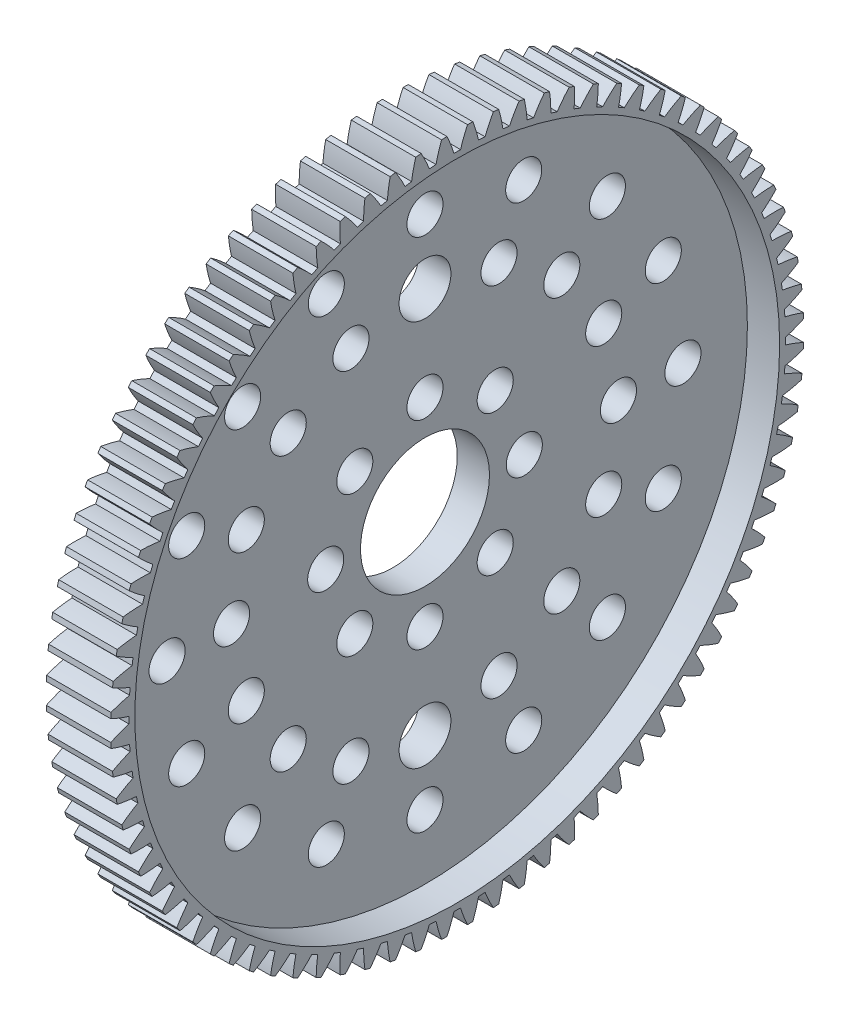
SolidWorks part; units mm, degrees
ref_plane "Plane1" through (0, 0, 0) normal (0, 0, 1) x (1, 0, 0)
ref_plane "Plane2" through (0, 0, 0) normal (0, 1, 0) x (1, 0, 0)
ref_plane "Plane3" through (0, 0, 0) normal (1, 0, 0) x (0, 0, -1)
sketch "HoldingSke" plane through (0, 0, 0) normal (0, 1, 0) x (1, 0, 0)
  line L0 (0, 0) -> (84.9607, -808.3474)
  line L1 (-15, 0) -> (100, 0) construction
  line L2 (0, 0) -> (-2.1039, 2.3779)
  line L3 (0, 0) -> (-11.863, 4.5341)
  line L4 (0, 0) -> (0.9027, 8.5887)
  line L5 (0, 0) -> (-47.5972, -17.7524)
  line L6 (0, 0) -> (-5.2639, -3.5516)
  line L7 (-2.1039, 2.3779) -> (8.8308, 51.9871)
  line L8 (-76.2, 54.61) -> (-61.976, 54.61)
  line L9 (-71.009, 38.7566) -> (-53.1078, 45.2721)
  line L10 (-76.2, 71.12) -> (104.1128, 71.12)
  line L11 (0, 0) -> (-6.35, 0)
  line L12 (-76.2, 101.6) -> (-76.1716, 101.6)
  line L13 (24.9733, 27.94) -> (52.9518, 28.4284)
  line L14 (24.9733, 27.94) -> (25.0241, 27.9398)
  line L15 (24.9733, 27.94) -> (100.4021, 29.52)
  circle A0 centre (0, 0) radius 6.35
  circle A1 centre (0, 0) radius 32.3342
  circle A2 centre (0, 0) radius 38.1
  circle A3 centre (0, 0) radius 6.35
  dimension "MHD" = 64.6684
  dimension "Hub_dia" = 76.2
  dimension "Bore" = 12.7
  dimension "MBD" = 12.7
  dimension "Num_teeth" = 84
  dimension "Pitch_radius" = 180.3128
  dimension "Pitch" = 812.8
  dimension "Width" = 6.35
  dimension "Overall_len" = 50.8
  dimension "Show_teeth" = 84
  dimension "Thickness" = 6.35
  dimension "OAL" = 50.8001
  dimension "T_dim" = 14.224
  dimension "Ap" = 20
  dimension "H" = 19.05
  dimension "Backlash" = 0.0284
  dimension "Addendum_fac" = 1
  dimension "Dedendum_fac" = 1.2
  dimension "Clearance_fac" = 0.2
  dimension "Dedendum_add" = 0.0508
sketch "BasProSke" plane through (0, 0, 0) normal (0, 1, 0) x (1, 0, 0)
  line L0 (-10, 0) -> (60, 0) construction
  line L1 (0, 0) -> (0, 34.1313)
  line L2 (0, 0) -> (6.35, 0)
  line L3 (6.35, 0) -> (6.35, 34.1313)
  line L4 (6.35, 34.1313) -> (0, 34.1313)
  dimension "Diameter" = 68.2625
  dimension "Thickness" = 6.35
revolve "Base-Revolve" add sketch "BasProSke" angle 360 about L0
sketch "TooCutSke" plane through (0, 0, 0) normal (1, 0, 0) x (0, 0, -1)
  line L1 (0, 0) -> (0, 107) construction
  line L2 (0, 0) -> (-0.6732, 33.3307) construction
  line L3 (0, 0) -> (-2.4927, 66.6185) construction
  line L4 (-0.6732, 33.3307) -> (-1.2463, 33.3093) construction
  arc A0 (0.3267, 32.3325) -> (-0.3267, 32.3325) centre (0, 0) ccw
  arc A1 (1.0224, 34.1413) -> (-1.0224, 34.1413) centre (0, 0) ccw
  circle A2 centre (0, 0) radius 33.3375 construction
  circle A3 centre (0, 0) radius 31.327 construction
  arc A4 (-0.3267, 32.3325) -> (-1.0224, 34.1413) centre (-13.0876, 28.4622) ccw
  arc A5 (1.0224, 34.1413) -> (0.3267, 32.3325) centre (13.0876, 28.4622) ccw
  dimension "Root_dia" = 64.6684
  dimension "Overcut_dia" = 68.3133
  dimension "Pitch_dia" = 66.675
  dimension "Base_dia" = 62.654
  dimension "Flank_rad" = 13.335
  dimension "Half_ang" = 2.143
  dimension "Half_CT" = 0.5736
extrude "ToothCut" cut sketch "TooCutSke" along normal through all
fillet "Breaks" [suppressed] radius 0.0159 tangent propagation no
fillet "RootFillets" [suppressed] radius 0.2095
pattern_circular "TeethCuts" count 84 every 4.286 about axis through (-10, 0, 0) along (1, 0, 0) of "ToothCut", "RootFillets", "Breaks"
sketch "HubNeaOneSke" plane through (0, 0, 0) normal (-1, 0, 0) x (0, 0, 1)
  circle A0 centre (0, 0) radius 32.3342
  dimension "Diameter" = 64.6684
extrude "HubNearOne" [suppressed] add sketch "HubNeaOneSke" along normal blind 44.4501
sketch "HubNeaBotSke" plane through (0, 0, 0) normal (-1, 0, 0) x (0, 0, 1)
  circle A0 centre (0, 0) radius 32.3342
  dimension "Diameter" = 64.6684
extrude "HubNearBoth" [suppressed] add sketch "HubNeaBotSke" along normal blind 22.225
ref_plane "FarPln" through (6.35, 0, 0) normal (1, 0, 0) x (0, 0, -1)
sketch "HubFarSke" plane through (6.35, 0, 0) normal (1, 0, 0) x (0, 0, -1)
  circle A0 centre (0, 0) radius 32.3342
  dimension "Diameter" = 64.6684
extrude "HubFar" [suppressed] add sketch "HubFarSke" along normal blind 22.225
sketch "BorSke" plane through (0, 0, 0) normal (1, 0, 0) x (0, 0, -1)
  circle A0 centre (0, 0) radius 6.35
  dimension "Diameter" = 12.7
extrude "Bore" cut sketch "BorSke" along normal mid plane 101.6001
sketch "KeySke" plane through (0, 0, 0) normal (1, 0, 0) x (0, 0, -1)
  line L0 (-1.5875, 0) -> (-1.5875, 7.874)
  line L1 (-1.5875, 7.874) -> (1.5875, 7.874)
  line L2 (1.5875, 7.874) -> (1.5875, 0)
  line L3 (0, 0) -> (0, 34) construction
  line L4 (-1.5875, 0) -> (1.5875, 0)
  dimension "Offset" = 7.874
  dimension "Width" = 3.175
extrude "Keyway" [suppressed] cut sketch "KeySke" along normal mid plane 101.6001
pattern_circular "Keyway2" [suppressed] count 2 every 90 about axis through (-10, 0, 0) along (1, 0, 0)
sketch "Sketch1" plane through (6.35, 0, 0) normal (1, 0, 0) x (0, 0, -1)
  line L0 (0, 0) -> (0, 50.8) construction
  circle A0 centre (0, 9.779) radius 1.778
  circle A1 centre (0, 19.05) radius 1.778
  circle A2 centre (0, 25.4) radius 1.778
  circle A3 centre (6.9148, 6.9148) radius 1.778
  circle A4 centre (9.779, 0) radius 1.778
  circle A5 centre (6.9148, -6.9148) radius 1.778
  circle A6 centre (0, -9.779) radius 1.778
  circle A7 centre (-6.9148, -6.9148) radius 1.778
  circle A8 centre (-9.779, 0) radius 1.778
  circle A9 centre (-6.9148, 6.9148) radius 1.778
  circle A10 centre (7.2901, 17.5999) radius 1.778
  circle A11 centre (9.7202, 23.4665) radius 1.778
  circle A12 centre (13.4704, 13.4704) radius 1.778
  circle A13 centre (17.9605, 17.9605) radius 1.778
  circle A14 centre (17.5999, 7.2901) radius 1.778
  circle A15 centre (23.4665, 9.7202) radius 1.778
  circle A16 centre (19.05, 0) radius 1.778
  circle A17 centre (25.4, 0) radius 1.778
  circle A18 centre (17.5999, -7.2901) radius 1.778
  circle A19 centre (23.4665, -9.7202) radius 1.778
  circle A20 centre (13.4704, -13.4704) radius 1.778
  circle A21 centre (17.9605, -17.9605) radius 1.778
  circle A22 centre (7.2901, -17.5999) radius 1.778
  circle A23 centre (9.7202, -23.4665) radius 1.778
  circle A24 centre (0, -19.05) radius 1.778
  circle A25 centre (0, -25.4) radius 1.778
  circle A26 centre (-7.2901, -17.5999) radius 1.778
  circle A27 centre (-9.7202, -23.4665) radius 1.778
  circle A28 centre (-13.4704, -13.4704) radius 1.778
  circle A29 centre (-17.9605, -17.9605) radius 1.778
  circle A30 centre (-17.5999, -7.2901) radius 1.778
  circle A31 centre (-23.4665, -9.7202) radius 1.778
  circle A32 centre (-19.05, 0) radius 1.778
  circle A33 centre (-25.4, 0) radius 1.778
  circle A34 centre (-17.5999, 7.2901) radius 1.778
  circle A35 centre (-23.4665, 9.7202) radius 1.778
  circle A36 centre (-13.4704, 13.4704) radius 1.778
  circle A37 centre (-17.9605, 17.9605) radius 1.778
  circle A38 centre (-7.2901, 17.5999) radius 1.778
  circle A39 centre (-9.7202, 23.4665) radius 1.778
  point P25 (0, 0)
  point P86 (0, 0)
  dimension "D1" = 50.8
  dimension "D2" = 9.779
  dimension "D3" = 19.05
  dimension "D4" = 25.4
  dimension "D5" = 3.556
  dimension "D6" = 3.556
  dimension "D7" = 3.556
  dimension "D8" = 8
  dimension "D9" = 16
extrude "Cut-Extrude1" cut sketch "Sketch1" against normal through all
sketch "Sketch2" plane through (6.35, 0, 0) normal (1, 0, 0) x (0, 0, -1)
  circle A0 centre (0, 0) radius 31.75
  dimension "D1" = 63.5
extrude "Cut-Extrude2" cut sketch "Sketch2" against normal blind 3.175
hole_wizard "1/4-20 Tapped Hole1" positions "3DSketch1" profile "Sketch3" tap size "1/4-20" standard "ANSI Inch"
sketch3d "3DSketch1"
  line L0 (0, 19.05, 0) -> (3.175, 19.05, 0) construction
  line L1 (0, -19.05, 0) -> (3.175, -19.05, 0) construction
  point P0 (3.175, 19.05, 0)
  point P4 (3.175, -19.05, 0)
sketch "Sketch3" plane through (3.175, 19.05, 0) normal (0, 1, 0) x (0, 0, -1)
  line L0 (0, 0) -> (0, 20.5838)
  line L1 (0, 20.5838) -> (2.5527, 19.05)
  line L2 (2.5527, 19.05) -> (2.5527, 0)
  line L5 (2.5527, 0) -> (0, 0)
  line L10 (0, 20.5838) -> (-2.5527, 19.05) construction
  line L11 (0, -6.35) -> (0, 107.95) construction
  dimension "Tap Drill Dia." = 5.1054
  dimension "Tap Drill Depth" = 19.05
  dimension "Drill Angle" = 118
cosmetic thread "Hole Thread1" parameters "D1"=3.175, "D2"=6.35
cosmetic thread "Hole Thread2" parameters "D1"=3.175, "D2"=6.35
equation "' \"Pitch@HoldingSke\" = 4"
equation "' \"Num_teeth@HoldingSke\" = 12"
equation "' \"Ap@HoldingSke\" =  20"
equation "' \"Width@HoldingSke\" = 0.5"
equation "' \"Hub_dia@HoldingSke\"= 1"
equation "' \"Overall_len@HoldingSke\" = 1.0"
equation "' \"Bore@HoldingSke\" = 0.75"
equation "' \"T_dim@HoldingSke\" = 0.85"
equation "' \"Width@KeySke\" = 0.25"
equation "' \"Show_teeth@HoldingSke\" = 13"
equation "' \"Backlash@HoldingSke\" = 0.009"
equation "' \"Addendum_fac@HoldingSke\" = 1.0"
equation "' \"Dedendum_fac@HoldingSke\" = 1.25"
equation "' \"Dedendum_add@HoldingSke\" = 0.00005"
equation "' \"Clearance_fac@HoldingSke\" = 0.25"
equation "' \"Pitch@HoldingSke\" = 0.5"
equation "' \"Num_teeth@HoldingSke\" = 23"
equation "' \"Show_teeth@HoldingSke\" = 23"
equation "' \"Backlash@HoldingSke\" = 0.0375"
equation "\"Overcut_dia@TooCutSke\" = (\"Num_teeth@HoldingSke\" + 2 * \"Addendum_fac@HoldingSke\") / \"Pitch@HoldingSke\" + 0.002"
equation "\"Pitch_dia@TooCutSke\" = \"Num_teeth@HoldingSke\" / \"Pitch@HoldingSke\""
equation "\"Base_dia@TooCutSke\" = \"Num_teeth@HoldingSke\" / \"Pitch@HoldingSke\" * cos((\"Ap@HoldingSke\"  * 3.14159265 / 180))"
equation "\"Root_dia@TooCutSke\" = (\"Num_teeth@HoldingSke\" + 2) / \"Pitch@HoldingSke\" - 2 * (\"Addendum_fac@HoldingSke\" + \"Dedendum_fac@HoldingSke\") / \"Pitch@HoldingSke\" - \"Dedendum_add@HoldingSke\" * 2"
equation "\"Half_ang@TooCutSke\" = 180 / \"Num_teeth@HoldingSke\""
equation "\"Half_CT@TooCutSke\" = \"Num_teeth@HoldingSke\" / \"Pitch@HoldingSke\" * sin((3.14159265 / 2 / \"Num_teeth@HoldingSke\")) / 2 - 7 * \"Backlash@HoldingSke\" / 4"
equation "\"Flank_rad@TooCutSke\" = \"Num_teeth@HoldingSke\" / \"Pitch@HoldingSke\" / 5"
equation "\"Radius@RootFillets\" = \"Clearance_fac@HoldingSke\" / \"Pitch@HoldingSke\" + \"Dedendum_add@HoldingSke\""
equation "\"Break_rad@Breaks\" = 0.02 / \"Pitch@HoldingSke\""
equation "\"Thickness@HoldingSke\" = \"Width@HoldingSke\""
equation "\"OAL@HoldingSke\" = \"Thickness@HoldingSke\""
equation "\"MHD@HoldingSke\" = (\"Num_teeth@HoldingSke\" + 2) / \"Pitch@HoldingSke\" - 2 * (\"Addendum_fac@HoldingSke\" + \"Dedendum_fac@HoldingSke\")  / \"Pitch@HoldingSke\" - \"Dedendum_add@HoldingSke\" * 2"
equation "\"MBD@HoldingSke\" = (\"Num_teeth@HoldingSke\" + 2) / \"Pitch@HoldingSke\" - 2 * (\"Addendum_fac@HoldingSke\" + \"Dedendum_fac@HoldingSke\")  / \"Pitch@HoldingSke\" - \"Dedendum_add@HoldingSke\" * 2 - 0.002"
equation "\"MHD@HoldingSke\" = ((sgn( \"MHD@HoldingSke\" - \"Hub_dia@HoldingSke\" )-1)*( \"MHD@HoldingSke\" - \"Hub_dia@HoldingSke\" ))/-2+ \"Hub_dia@HoldingSke\""
equation "\"MBD@HoldingSke\" = ((sgn( \"MBD@HoldingSke\" - \"Bore@HoldingSke\" )-1)*( \"MBD@HoldingSke\" - \"Bore@HoldingSke\" ))/-2+ \"Bore@HoldingSke\""
equation "\"OAL@HoldingSke\" = ((sgn( \"OAL@HoldingSke\" - \"Overall_len@HoldingSke\" )+1)*( \"OAL@HoldingSke\" - \"Overall_len@HoldingSke\" ))/2 + \"Overall_len@HoldingSke\" + 0.000002"
equation "\"Num_teeth@TeethCuts\" = int( \"Show_teeth@HoldingSke\" ) + 1"
equation "\"Num_teeth@TeethCuts\" = ((sgn( \"Num_teeth@TeethCuts\" - \"Num_teeth@HoldingSke\" )-1)*( \"Num_teeth@TeethCuts\" - \"Num_teeth@HoldingSke\" ))/-2+ \"Num_teeth@HoldingSke\""
equation "\"Num_teeth@TeethCuts\" = ((sgn( \"Num_teeth@TeethCuts\" - 2.0)+1)*( \"Num_teeth@TeethCuts\" - 2.0))/2 +2.0"
equation "\"Angle@TeethCuts\" = 360.0 / \"Num_teeth@HoldingSke\""
equation "\"Diameter@BasProSke\" = (\"Num_teeth@HoldingSke\" + 2 * \"Addendum_fac@HoldingSke\") / \"Pitch@HoldingSke\""
equation "\"Thickness@BasProSke\"  = \"Thickness@HoldingSke\""
equation "' \"Fillet_rad@BasProSke\" =  \"Thickness@HoldingSke\" * 0.05"
equation "\"MHD@HoldingSke\" = ((sgn( \"MHD@HoldingSke\" - \"Root_dia@TooCutSke\" )-1)*( \"MHD@HoldingSke\" - \"Root_dia@TooCutSke\" ))/-2+ \"Root_dia@TooCutSke\""
equation "\"Diameter@HubNeaOneSke\" = \"MHD@HoldingSke\""
equation "\"Length@HubNearOne\" = \"OAL@HoldingSke\" - \"Thickness@BasProSke\""
equation "\"Diameter@HubNeaBotSke\" = \"MHD@HoldingSke\""
equation "\"Length@HubNearBoth\" = ( \"OAL@HoldingSke\" - \"Thickness@BasProSke\" ) / 2.0"
equation "\"Thickness@FarPln\" = \"Thickness@BasProSke\""
equation "\"Diameter@HubFarSke\" = \"MHD@HoldingSke\""
equation "\"Length@HubFar\" = ( \"OAL@HoldingSke\" - \"Thickness@BasProSke\" ) / 2.0"
equation "\"Diameter@BorSke\" = \"MBD@HoldingSke\""
equation "\"D1@Bore\" = \"OAL@HoldingSke\" * 2.0"
equation "\"D1@Keyway\" = \"OAL@HoldingSke\" * 2.0"
equation "\"Offset@KeySke\" = \"T_dim@HoldingSke\" - \"MBD@HoldingSke\" / 2.0"
